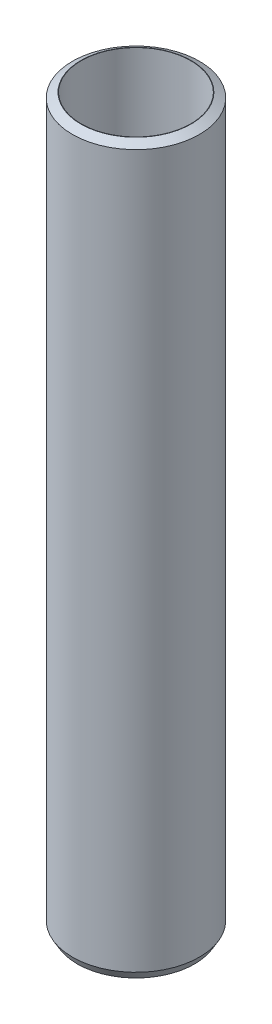
SolidWorks part; units mm, degrees
ref_plane "Front Plane" through (0, 0, 0) normal (0, 0, 1) x (1, 0, 0)
ref_plane "Top Plane" through (0, 0, 0) normal (0, 1, 0) x (1, 0, 0)
ref_plane "Right Plane" through (0, 0, 0) normal (1, 0, 0) x (0, 0, -1)
sketch "Sketch1" plane through (0, 0, 0) normal (0, 1, 0) x (1, 0, 0)
  circle A0 centre (0, 0) radius 52.5
  dimension "SHAFT_OD" = 105
extrude "Boss-Extrude1" add sketch "Sketch1" along normal blind 600
sketch "Sketch2" plane through (0, 0, 0) normal (0, 1, 0) x (1, 0, 0)
  circle A0 centre (0, 0) radius 45.2888
  dimension "BORE_D" = 90.5776
extrude "Cut-Extrude1" cut sketch "Sketch2" along normal through all
chamfer "Chamfer1" distance 3.9907 angle 60 2 edges at (0, 600, 52.5) (0, 0, 52.5) first distance on face at (0, 600, 52.5) first distance on face at (0, 0, 45.2888)
